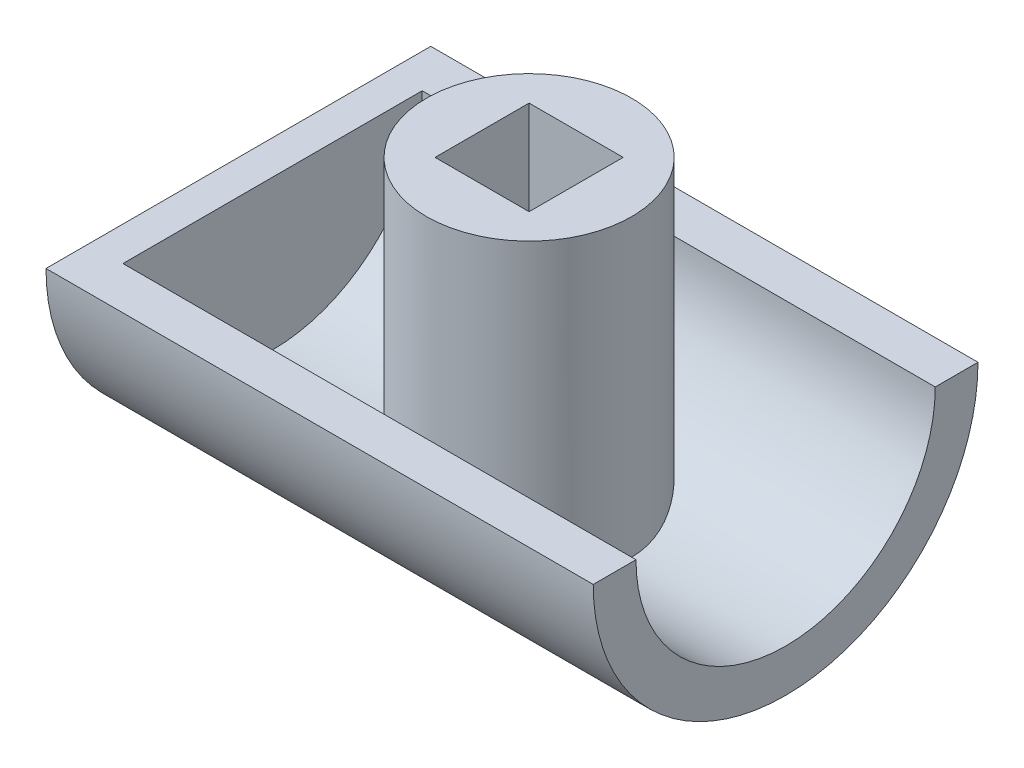
SolidWorks part; units mm, degrees
ref_plane "Front Plane" through (0, 0, 0) normal (0, 0, 1) x (1, 0, 0)
ref_plane "Top Plane" through (0, 0, 0) normal (0, 1, 0) x (1, 0, 0)
ref_plane "Right Plane" through (0, 0, 0) normal (1, 0, 0) x (0, 0, -1)
sketch "Sketch1" plane through (0, 0, 0) normal (1, 0, 0) x (0, 0, -1)
  line L0 (0, 46.5426) -> (0, -61.5196) construction
  line L1 (-65.5956, 0) -> (59.529, 0) construction
  line L2 (-17.5, 0) -> (-22.5, 0)
  line L3 (17.5, 0) -> (22.5, 0)
  arc A0 (-17.5, 0) -> (17.5, 0) centre (0, 0) ccw
  arc A1 (-22.5, 0) -> (22.5, 0) centre (0, 0) ccw
  dimension "D2" = 17.5
  dimension "D1" = 5
extrude "Boss-Extrude1" add sketch "Sketch1" along normal blind 30 and the other way blind 30
sketch "Sketch3" plane through (0, 0, 0) normal (0, 1, 0) x (1, 0, 0)
  line L2 (30, 0) -> (6.125, 0) construction
  line L4 (30, 17.5) -> (30, -17.5) construction
  circle A0 centre (0, 0) radius 12
  dimension "D1" = 24
extrude "Boss-Extrude2" add sketch "Sketch3" against normal up to surface and the other way blind 17 up to face at (0, -8.75, 0)
sketch "Sketch4" plane through (-30, 0, 0) normal (-1, 0, 0) x (0, 0, 1)
  line L6 (-22.5, 0) -> (22.5, 0)
  arc A0 (-22.5, 0) -> (22.5, 0) centre (0, 0) ccw
extrude "Boss-Extrude3" add sketch "Sketch4" along normal blind 4
sketch "Sketch5" plane through (0, 17, 0) normal (0, 1, 0) x (1, 0, 0)
  line L0 (0, 12) -> (0, -12) construction
  line L1 (-12, 0) -> (12, 0) construction
  line L3 (5.5, -5.5) -> (-5.5, -5.5)
  line L4 (5.5, -5.5) -> (5.5, 5.5)
  line L5 (5.5, 5.5) -> (-5.5, 5.5)
  line L6 (-5.5, -5.5) -> (-5.5, 5.5)
  line L7 (5.5, -5.5) -> (-5.5, 5.5) construction
  line L8 (5.5, 5.5) -> (-5.5, -5.5) construction
  circle A0 centre (0, 0) radius 12 construction
  circle A1 centre (0, 0) radius 12 construction
  point P9 (0, 0)
  dimension "D1" = 11
  dimension "D2" = 11
extrude "Cut-Extrude1" cut sketch "Sketch5" against normal blind 17
